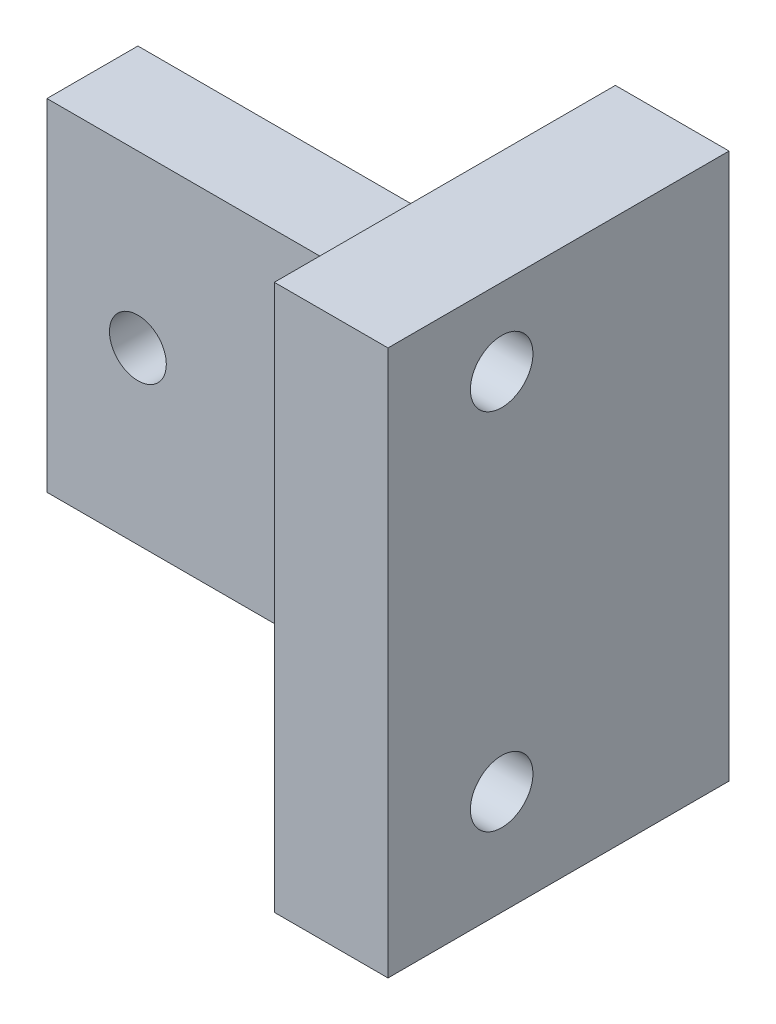
SolidWorks part; units mm, degrees
ref_plane "Plan de face" through (0, 0, 0) normal (0, 0, 1) x (1, 0, 0)
ref_plane "Plan de dessus" through (0, 0, 0) normal (0, 1, 0) x (1, 0, 0)
ref_plane "Plan de droite" through (0, 0, 0) normal (1, 0, 0) x (0, 0, -1)
sketch "Sketch1" plane through (0, 0, 0) normal (0, 0, 1) x (1, 0, 0)
  line L1 (0, 0) -> (42, 0)
  line L2 (0, 0) -> (0, 30)
  line L3 (0, 30) -> (42, 30)
  line L4 (42, 0) -> (42, 30)
  line L5 (42, 0) -> (52, 0)
  line L6 (42, 0) -> (42, 148)
  line L7 (42, 148) -> (52, 148)
  line L8 (52, 0) -> (52, 148)
  line L9 (42, 148) -> (0, 148)
  line L10 (42, 148) -> (42, 118)
  line L11 (42, 118) -> (0, 118)
  line L12 (0, 148) -> (0, 118)
  dimension "D1" = 42
  dimension "D2" = 30
  dimension "D3" = 42
  dimension "D4" = 30
  dimension "D5" = 148
  dimension "D6" = 10
extrude "Boss-Extrude1" add sketch "Sketch1" along normal blind 8 contours L9 L12 L11 L6 | L1 L4 L3 L2 region at (21, 15, 0) region at (21, 133, 0)
extrude "Boss-Extrude2" add sketch "Sketch1<3>" along normal blind 30 contours L5 L8 L7 L6 L4 region at (47, 74, 0)
sketch "Sketch1<3>" plane through (0, 0, 0) normal (0, 0, 1) x (1, 0, 0) same geometry as "Sketch1"
sketch "Sketch2" plane through (0, 0, 8) normal (0, 0, 1) x (1, 0, 0)
  line L0 (42, 148) -> (0, 148) construction
  line L1 (0, 148) -> (0, 118) construction
  line L2 (42, 0) -> (42, 148) construction
  line L3 (52, 74) -> (0, 74) construction
  line L4 (52, 0) -> (52, 148) construction
  circle A0 centre (8, 133) radius 2.5
  circle A1 centre (34, 133) radius 2.5
  circle A2 centre (34, 15) radius 2.5
  circle A3 centre (8, 15) radius 2.5
  dimension "D1" = 5
  dimension "D2" = 5
  dimension "D3" = 15
  dimension "D4" = 8
  dimension "D5" = 8
extrude "Cut-Extrude1" cut sketch "Sketch2" against normal up to surface (8 mm away) up to face at (26.125, 68.5, 0)
sketch "Sketch3" plane through (52, 0, 0) normal (1, 0, 0) x (0, 0, -1)
  line L1 (-30, 148) -> (0, 148) construction
  line L2 (-30, 0) -> (-30, 148) construction
  circle A0 centre (-20, 138.3) radius 2.75
  circle A1 centre (-20, 106.3) radius 2.75
  circle A2 centre (-20, 41.2) radius 2.75
  circle A3 centre (-20, 9.2) radius 2.75
  dimension "D2" = 5.5
  dimension "D3" = 5.5
  dimension "D10" = 5.5
  dimension "D11" = 5.5
  dimension "D1" = 32
  dimension "D4" = 9.7
  dimension "D5" = 10
  dimension "D6" = 65.1
  dimension "D7" = 32
  dimension "D8" = 10
  dimension "D9" = 10
extrude "Cut-Extrude2" cut sketch "Sketch3" against normal up to surface (10 mm away) up to face at (42, 66.625, 13.375)
sketch "Sketch4" plane through (52, 0, 0) normal (1, 0, 0) x (0, 0, -1)
  line L0 (-30, 0) -> (-30, 148) construction
  line L1 (0, 48) -> (-30, 48)
  line L2 (0, 48) -> (0, 148)
  line L3 (0, 148) -> (-30, 148)
  line L4 (-30, 48) -> (-30, 148)
  line L5 (0, 0) -> (0, 148) construction
  dimension "D1" = 100
extrude "Cut-Extrude3" cut sketch "Sketch4" against normal blind 52
